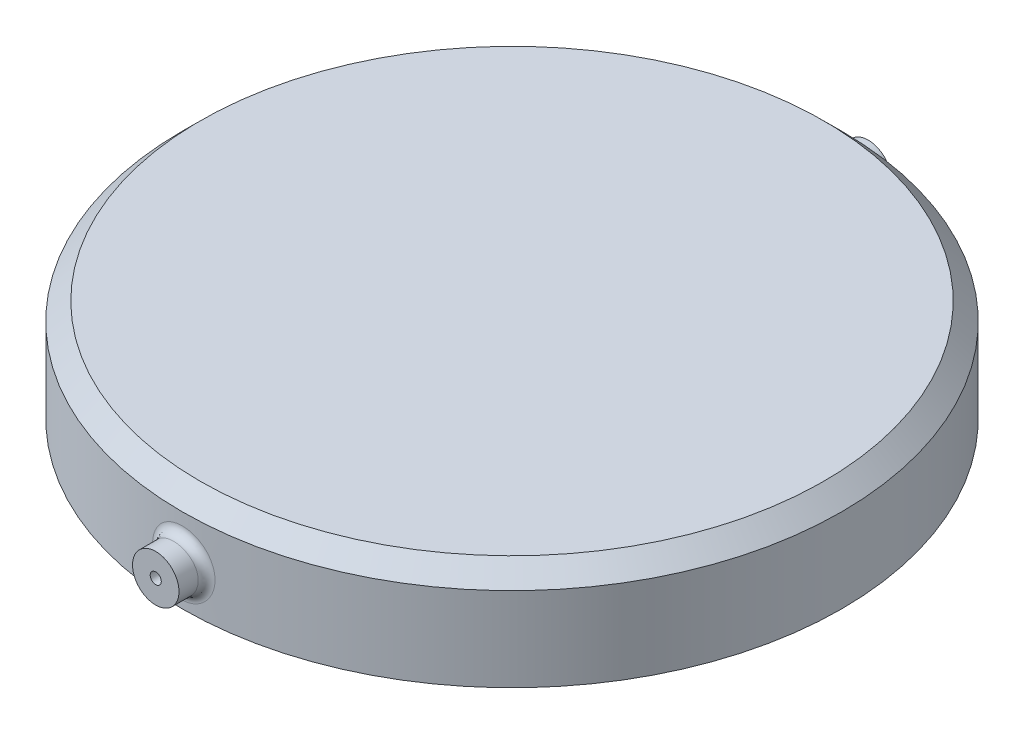
SolidWorks part; units mm, degrees
ref_plane "Front Plane" through (0, 0, 0) normal (0, 0, 1) x (1, 0, 0)
ref_plane "Top Plane" through (0, 0, 0) normal (0, 1, 0) x (1, 0, 0)
ref_plane "Right Plane" through (0, 0, 0) normal (1, 0, 0) x (0, 0, -1)
sketch "Sketch1" plane through (0, 0, 0) normal (0, 1, 0) x (1, 0, 0)
  line L0 (0, 0) -> (0, 13.7725) construction
  line L1 (0, 0) -> (-10.9504, 0) construction
  circle A0 centre (0, 0) radius 35.5
  circle A1 centre (0, 0) radius 35 construction
  circle A2 centre (0, 0) radius 37.25
  circle A3 centre (0, 0) radius 30
  dimension "D1" = 71
  dimension "D2" = 70
  dimension "D3" = 1.75
  dimension "D4" = 60
extrude "Boss-Extrude1" add sketch "Sketch1" against normal blind 10 contours A2 A0 region at (-36.1964, 0, 0)
extrude "Boss-Extrude2" add sketch "Sketch1<2>" along normal blind 1.5 contours A0 | A2 A0 | A3 region at (-34.4959, 0, 0) region at (-36.1964, 0, 0) region at (0, 0, 0)
sketch "Sketch1<2>" plane through (0, 0, 0) normal (0, 1, 0) x (1, 0, 0) same geometry as "Sketch1"
chamfer "Chamfer1" distance 1.5 angle 45 1 edges at (0, 0, 35.5)
chamfer "Chamfer2" distance 2 angle 45 1 edges at (0, 1.5, 37.25)
ref_plane "Plane1" through (0, 0, 37.25) normal (0, 0, 1) x (1, 0, 0)
sketch "Sketch2" plane through (0, 0, 37.25) normal (0, 0, 1) x (1, 0, 0)
  line L0 (0, -0.5) -> (0, -10) construction
  line L1 (-37.25, -0.5) -> (37.25, -0.5) construction
  line L2 (-37.25, -10) -> (37.25, -10) construction
  circle A0 centre (0, -5.5) radius 0.625
  circle A1 centre (0, -5.5) radius 2.625
  dimension "D1" = 1.25
  dimension "D2" = 2
  dimension "D3" = 5
extrude "Cut-Extrude1" cut sketch "Sketch2" against normal blind 10 contours L0 A0 | A0 L0 region at (0.2653, -5.5, 37.25) region at (-0.2653, -5.5, 37.25)
extrude "Boss-Extrude4" add sketch "Sketch2<3>" along normal blind 3 and the other way blind 1 contours A1 L0 A0 | L0 A1 A0 region at (1.1651, -5.5, 37.25) region at (-1.1651, -5.5, 37.25)
sketch "Sketch2<3>" plane through (0, 0, 37.25) normal (0, 0, 1) x (1, 0, 0) same geometry as "Sketch2"
mirror "Mirror1" about plane through (0, 0, 0) normal (0, 0, 1) of "Boss-Extrude4", "Cut-Extrude1"
ref_plane "Plane2" through (37.25, 0, 0) normal (1, 0, 0) x (0, 0, -1)
sketch "tirangle" plane through (37.25, 0, 0) normal (1, 0, 0) x (0, 0, -1)
  line L0 (0, -0.5) -> (0, -13.8889) construction
  line L2 (2.5, -0.5) -> (-2.5, -0.5)
  line L6 (-2.5, -0.5) -> (0, -3)
  line L7 (-37.25, -0.5) -> (37.25, -0.5) construction
  line L8 (0, -3) -> (2.5, -0.5)
  dimension "D1" = 45
  dimension "D2" = 5
extrude "Boss-Extrude6" add sketch "tirangle" against normal blind 5 from offset 1 offset against normal yes
mirror "Mirror2" about plane through (0, 0, 0) normal (1, 0, 0) of "Boss-Extrude6"
fillet "Fillet1" radius 1 2 edges at (2.5563, -4.9036, -37.1622) (-0.5964, -2.9437, 37.2452)
